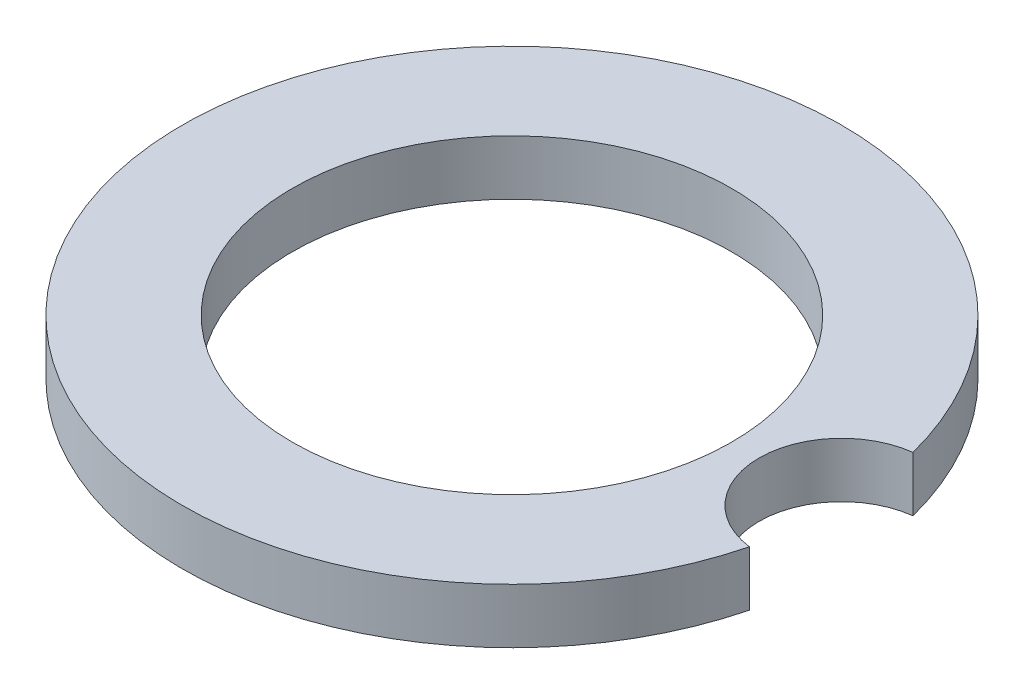
SolidWorks part; units mm, degrees
ref_plane "Front Plane" through (0, 0, 0) normal (0, 0, 1) x (1, 0, 0)
ref_plane "Top Plane" through (0, 0, 0) normal (0, 1, 0) x (1, 0, 0)
ref_plane "Right Plane" through (0, 0, 0) normal (1, 0, 0) x (0, 0, -1)
sketch "Sketch1" plane through (0, 0, 0) normal (0, 1, 0) x (1, 0, 0)
  circle A0 centre (0, 0) radius 50.8
  circle A1 centre (0, 0) radius 76.1746
  dimension "Front_CR_ID" = 101.6
  dimension "Front_CR_OD" = 152.3492
extrude "Boss-Extrude1" add sketch "Sketch1" along normal blind 12.7 contours A1
extrude "Cut-Extrude2" cut sketch "Sketch1<10>" along normal through all contours A0
sketch "Sketch1<10>" plane through (0, 0, 0) normal (0, 1, 0) x (1, 0, 0) same geometry as "Sketch1"
sketch "Sketch2" plane through (0, 12.7, 0) normal (0, 1, 0) x (1, 0, 0)
  line L0 (76.2, 19.05) -> (76.2, -19.05)
  arc A0 (76.2, 19.05) -> (76.2, -19.05) centre (76.1746, 0) ccw
  circle A1 centre (0, 0) radius 76.1746 construction
  dimension "D1" = 38.1
extrude "Cut-Extrude3" cut sketch "Sketch2" against normal through all contours A0 L0
ref_plane "Plane1" through (0, 6.35, 0) normal (0, -1, 0) x (-1, 0, 0)
equation "\"Bodytube_OD\" = 6.17in"
equation "\"Bodytube_ID\" = 5.998in"
equation "\"Motor_OD\" = 4in"
equation "\"Fwd_Tube_Length\" = 40in"
equation "\"Mid_Tube_Length\" = 1in"
equation "\"Aft_Section_Length\"= 39in"
equation "\"Mid_Coupler_Length\"= 13in"
equation "\"Aft_Lower_Length\"= 22in"
equation "\"AB_Coupler_OD_Length\"= 1in"
equation "\"AB_Coupling_Section_Length\"= 0.375in"
equation "\"AB_Coupler_Length\"= \"AB_Coupler_OD_Length\" + \"AB_Coupling_Section_Length\" * 2"
equation "\"Cutout_Angle\" = 80"
equation "\"AB_Paddle_Height\" = 0.575in"
equation "\"AB_Coupler_Num_Screws\"= 6"
equation "\"Num_Cutouts\" = 3"
equation "\"AB_Coupler_OD\"= 6.17in"
equation "\"AB_Coupler_ID\"= 5.75in"
equation "\"AB_Coupler_Surface_Diameter\"= 5.998in"
equation "\"AB_Coupling_Screw_Diameter\"= 0.1065in"
equation "\"AB_Central_Bushing_Length\" = .75in"
equation "\"Lead_Screw_Dist\" = 2.25in"
equation "\"Lead_Screw_Diam\" = 11mm"
equation "\"Lead_Screw_Length\" = (\"Mid_Coupler_Length\" + 2*0.375in + 2*0.5in)"
equation "\"Paddle_Pin_Offset\" = .25in"
equation "\"Paddle_Pin_Radius\" = 2.25in"
equation "\"Paddle_Gear_OD\" = 3.2in"
equation "\"Fwd_BKHD_From_Top\" = 18in"
equation "\"Front_CR_OD@Sketch1\"=\"Bodytube_ID\""
equation "\"Front_CR_ID@Sketch1\"=\"Motor_OD\""
